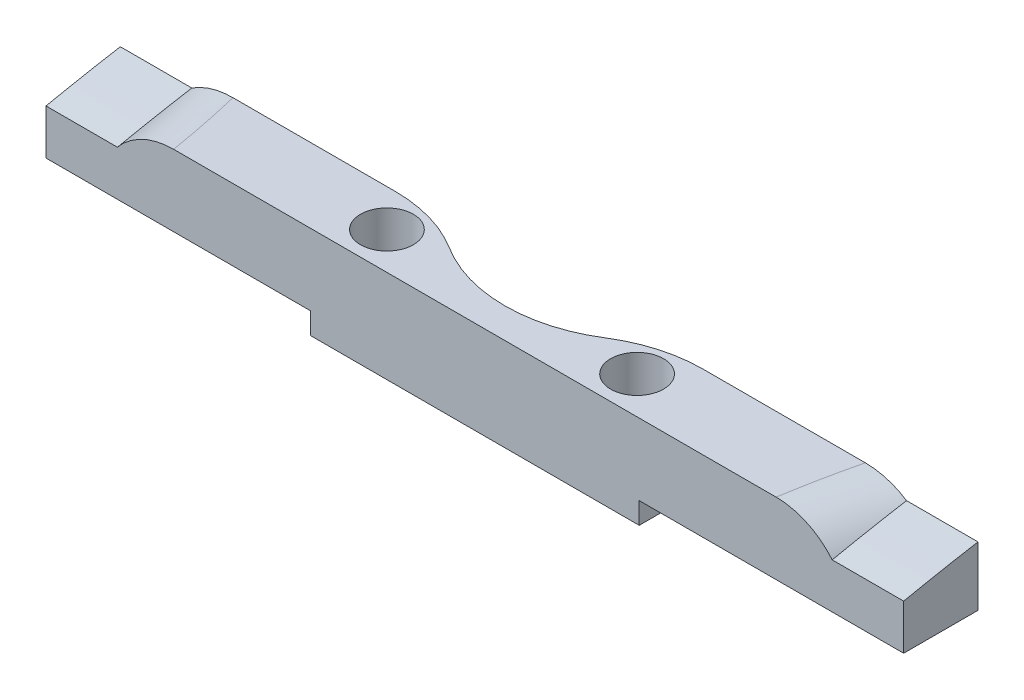
SolidWorks part; units mm, degrees
ref_plane "Ebene vorne" through (0, 0, 0) normal (0, 0, 1) x (1, 0, 0)
ref_plane "Ebene oben" through (0, 0, 0) normal (0, 1, 0) x (1, 0, 0)
ref_plane "Ebene rechts" through (0, 0, 0) normal (1, 0, 0) x (0, 0, -1)
sketch "Skizze1" plane through (0, 0, 0) normal (0, 1, 0) x (1, 0, 0)
  line L0 (-60, 0) -> (60, 0)
  line L1 (60, 0) -> (60, 10.4)
  line L2 (60, 10.4) -> (14.6843, 10.4)
  line L3 (0, 10) -> (0, 0) construction
  line L4 (-60, 0) -> (-60, 10.4)
  line L5 (-14.6843, 10.4) -> (-60, 10.4)
  arc A0 (14.6843, 10.4) -> (0, 4.2) centre (0, 24.6893) cw
  arc A1 (-14.6843, 10.4) -> (0, 4.2) centre (0, 24.6893) ccw
  dimension "D3" = 4.2
  dimension "D1" = 120
  dimension "D2" = 10.4
extrude "Aufsatz-Linear austragen1" add sketch "Skizze1" along normal blind 10
sketch "Skizze7" plane through (0, 0, 0) normal (0, -1, 0) x (1, 0, 0)
  line L0 (0, 0) -> (0, -22.0534) construction
  line L1 (23, 0) -> (23, -10.4)
  line L2 (-60, 0) -> (60, 0) construction
  line L3 (60, -10.4) -> (14.6843, -10.4) construction
  line L4 (23, -10.4) -> (14.6843, -10.4)
  line L5 (23, 0) -> (-23, 0)
  line L6 (-23, -10.4) -> (-14.6843, -10.4)
  line L7 (-23, 0) -> (-23, -10.4)
  arc A0 (14.6843, -10.4) -> (-14.6843, -10.4) centre (0, -24.6893) ccw
  arc A1 (14.6843, -10.4) -> (-14.6843, -10.4) centre (0, -24.6893) ccw construction
  dimension "D1" = 46
extrude "Aufsatz-Linear austragen2" add sketch "Skizze7" along normal blind 3
sketch "Skizze3" plane through (0, 10, 0) normal (0, 1, 0) x (1, 0, 0)
  line L0 (0, 0) -> (0, 22.3064) construction
  line L1 (17.5, 5.2) -> (-17.5, 5.2) construction
  line L2 (0, 12.2) -> (0, 4.2) construction
  circle A0 centre (17.5, 5.2) radius 2.1
  circle A1 centre (0, 12.2) radius 2.5 construction
  circle A2 centre (-17.5, 5.2) radius 2.1
  arc A3 (-14.6843, 10.4) -> (14.6843, 10.4) centre (0, 24.6893) ccw construction
  dimension "D1" = 4.2
  dimension "D4" = 5
  dimension "D2" = 35
  dimension "D3" = 7
  dimension "D5" = 8
extrude "Schnitt-Linear austragen1" cut sketch "Skizze3" against normal through all contours A0 | A2 region at (17.5, 10, -5.2)
sketch "Skizze4" plane through (-60, 0, 0) normal (1, 0, 0) x (0, 0, -1)
  line L0 (0, 10) -> (10.4, 10)
  line L1 (10.4, 10) -> (10.4, 8.2965)
  line L2 (10.4, 10) -> (10.4, 0) construction
  line L3 (0, 10) -> (0, 6.32)
  line L4 (0, 10) -> (0, 0) construction
  arc A1 (0, 6.32) -> (10.4, 8.2965) centre (58.0172, -270.6068) cw
extrude "Schnitt-Linear austragen2" cut sketch "Skizze4" along normal blind 10
fillet "Verrundung1" radius 10 1 edges at (-50, 10, -5.2)
mirror "Spiegeln1" about plane through (0, 0, 0) normal (1, 0, 0) of "Schnitt-Linear austragen2", "Verrundung1"
sketch "Skizze5" plane through (0, 10, 0) normal (0, 1, 0) x (1, 0, 0)
  circle A0 centre (-17.5, 5.2) radius 3.7
  circle A1 centre (17.5, 5.2) radius 3.7
  dimension "D1" = 7.4
extrude "Schnitt-Linear austragen3" cut sketch "Skizze5" against normal blind 6
fillet "Verrundung2" radius 20 2 edges at (14.6843, 3.5, -10.4) (-14.6843, 3.5, -10.4)
sketch "Skizze6" plane through (0, 0, 0) normal (0, -1, 0) x (1, 0, 0)
  line L1 (-24.9478, 11.0453) -> (24.9478, 11.0453)
  line L2 (-24.9478, 11.0453) -> (-24.9478, -11.0453)
  line L3 (-24.9478, -11.0453) -> (24.9478, -11.0453)
  line L4 (24.9478, 11.0453) -> (24.9478, -11.0453)
  line L5 (-24.9478, 11.0453) -> (24.9478, -11.0453) construction
  line L6 (-24.9478, -11.0453) -> (24.9478, 11.0453) construction
  point P0 (0, 0)
extrude "Schnitt-Linear austragen4" [suppressed] cut sketch "Skizze6" against normal blind 2.5
fillet "Verrundung3" [suppressed] radius 1.5 tangent propagation no
